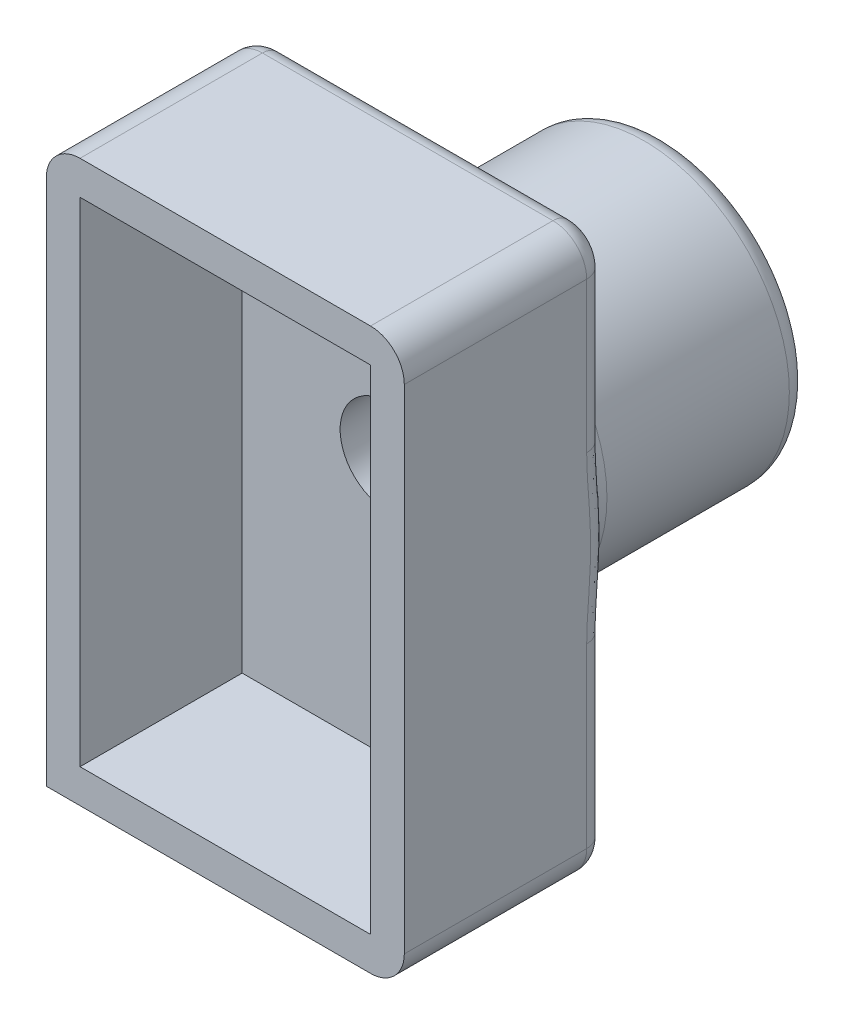
SolidWorks part; units mm, degrees
ref_plane "Front Plane" through (0, 0, 0) normal (0, 0, 1) x (1, 0, 0)
ref_plane "Top Plane" through (0, 0, 0) normal (0, 1, 0) x (1, 0, 0)
ref_plane "Right Plane" through (0, 0, 0) normal (1, 0, 0) x (0, 0, -1)
sketch "Sketch1" plane through (0, 0, 0) normal (0, 0, 1) x (1, 0, 0)
  line L1 (5.461, -9.271) -> (-5.461, -9.271)
  line L2 (5.461, -9.271) -> (5.461, 9.271)
  line L3 (5.461, 9.271) -> (-5.461, 9.271)
  line L4 (-5.461, -9.271) -> (-5.461, 9.271)
  line L5 (5.461, -9.271) -> (-5.461, 9.271) construction
  line L6 (5.461, 9.271) -> (-5.461, -9.271) construction
  point P0 (0, 0)
extrude "Boss-Extrude1" add sketch "Sketch1" along normal blind 1.524
sketch "Sketch3" plane through (0, 0, 0) normal (0, 0, 1) x (1, 0, 0)
  line L0 (0, 0) -> (0, 0.508) construction
  circle A2 centre (0, 0.508) radius 1.778
  circle A3 centre (0, 0.508) radius 5.461
extrude "Boss-Extrude2" add sketch "Sketch3" against normal blind 8.89
sketch "Sketch2" plane through (0, 0, 0) normal (0, 0, 1) x (1, 0, 0)
  line L1 (-5.461, -9.271) -> (5.461, -9.271)
  line L2 (-5.461, -9.271) -> (-5.461, 9.271)
  line L3 (-5.461, 9.271) -> (5.461, 9.271)
  line L4 (5.461, -9.271) -> (5.461, 9.271)
  line L5 (-5.461, -9.271) -> (5.461, 9.271) construction
  line L6 (-5.461, 9.271) -> (5.461, -9.271) construction
  point P0 (0, 0)
extrude "Extrude-Thin1" add sketch "Sketch2" along normal blind 7.62 thin thin type one direction wall 1.27
ref_plane "Plane1" through (0, 0, -8.89) normal (0, 0, -1) x (-1, 0, 0)
sketch "Sketch4" plane through (0, 0, -8.89) normal (0, 0, -1) x (-1, 0, 0)
  circle A0 centre (0, 0.508) radius 1.778
extrude "Cut-Extrude1" cut sketch "Sketch4" against normal blind 20.32
fillet "Fillet1" radius 1.27 4 edges at (5.461, 0.508, 0) (6.731, -10.541, 3.81) (6.731, 10.541, 3.81) (-6.731, 10.541, 3.81)
fillet "Fillet2" radius 0.762 1 edges at (5.461, 0.508, -8.89)
fillet "Fillet3" radius 0.762 9 edges at (-6.731, 4.8895, 0) (-6.359, 10.169, 0) (0, 10.541, 0) (6.359, 10.169, 0) (6.731, 4.8895, 0) (6.731, -4.3815, 0) (6.359, -10.169, 0) (-0.635, -10.541, 0) (-6.731, -5.0165, 0)
ref_plane "Plane2" through (0, 0, 0) normal (0, 0, -1) x (-1, 0, 0)
sketch "Sketch5" plane through (0, 0, 0) normal (0, 0, -1) x (-1, 0, 0)
  line L1 (3.3906, -7.8487) -> (5.164, -8.8727)
  line L2 (5.164, -8.8727) -> (5.164, -6.8248)
  line L3 (5.164, -6.8248) -> (3.3906, -7.8487)
  circle A0 centre (4.5729, -7.8487) radius 0.5912 construction
extrude "Cut-Extrude2" cut sketch "Sketch5" against normal blind 0.635 contours L1 L2 L3
